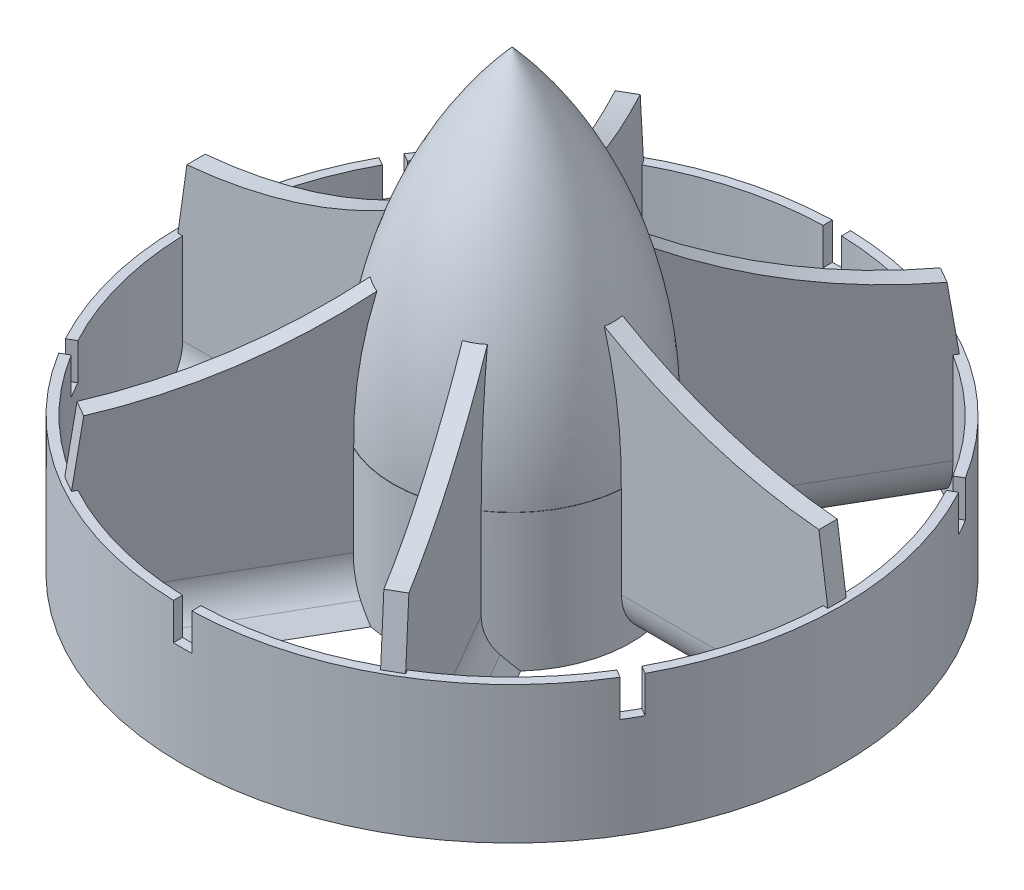
SolidWorks part; units mm, degrees
ref_plane "Ön Düzlem" through (0, 0, 0) normal (0, 0, 1) x (1, 0, 0)
ref_plane "Üst Düzlem" through (0, 0, 0) normal (0, 1, 0) x (1, 0, 0)
ref_plane "Sağ Düzlem" through (0, 0, 0) normal (1, 0, 0) x (0, 0, -1)
sketch "Çizim1" plane through (0, 0, 0) normal (0, 1, 0) x (1, 0, 0)
  circle A0 centre (0, 0) radius 13
  circle A1 centre (0, 0) radius 35
  circle A2 centre (0, 0) radius 36
  dimension "D1" = 26
  dimension "D2" = 70
extrude "Yükseklik-Ekstrüzyon1" add sketch "Çizim1" along normal blind 15 contours A0 region at (0, 0, 0)
extrude "Yükseklik-Ekstrüzyon2" add sketch "Çizim1<3>" along normal blind 15 separate body contours A2 | A1
sketch "Çizim1<3>" plane through (0, 0, 0) normal (0, 1, 0) x (1, 0, 0) same geometry as "Çizim1"
sketch "Çizim4" plane through (0, 0, 0) normal (1, 0, 0) x (0, 0, -1)
  line L1 (-36, 0) -> (36, 0) construction
  line L4 (1, 3) -> (1, 38)
  line L5 (1, 38) -> (-1, 38)
  line L6 (-1, 38) -> (-1, 0)
  line L8 (-1, 0) -> (4, 0)
  line L9 (4, 0) -> (1, 3)
  dimension "D2" = 2
extrude "Yükseklik-Ekstrüzyon5" add sketch "Çizim4" along normal blind 35.5 contours L5 L6 L8 L9 L4
fillet "Radyus5" radius 5 1 edges at (23.9736, 0, 1)
fillet "Radyus6" radius 5 1 edges at (23.9736, 3, -1)
ref_axis "Eksen1" through (0, 70.3345, 0) along (0, -1, 0)
pattern_circular "Dairesel Kaplama1" count 6 over 360 about axis through (0, 70.3345, 0) along (0, -1, 0) of "Yükseklik-Ekstrüzyon5", "Radyus5", "Radyus6"
sketch "Çizim8" plane through (0, 0, 0) normal (0, 0, 1) x (1, 0, 0)
  line L3 (35.5, 38) -> (35.5, 21.8859)
  line L4 (35.5, 38) -> (35.5, 15) construction
  line L5 (35.5, 38) -> (1.7321, 38) construction
  line L6 (0, 38) -> (35.5, 38)
  line L7 (16.884, 38) -> (0, 38) construction
  arc A0 (35.5, 21.8859) -> (0, 38) centre (39.5056, 77.8713) cw
extrude "Kes-Ekstrüzyon1" cut sketch "Çizim8" against normal blind 1 and the other way blind 1
pattern_circular "Dairesel Kaplama2" count 6 over 360 about axis through (0, 70.3345, 0) along (0, -1, 0) of "Kes-Ekstrüzyon1"
sketch "Çizim12" plane through (0, 0, 0) normal (0, 0, 1) x (1, 0, 0)
  line L0 (0, 15) -> (12.97, 15)
  line L1 (36, 15) -> (-36, 15) construction
  line L2 (0, 15) -> (0, 49.8724)
  line L3 (0, 70.3345) -> (0, -0.3415) construction
  arc A0 (0, 49.8724) -> (12.97, 15) centre (-38.174, 15.8263) cw
revolve "Döndür1" add sketch "Çizim12" angle 360 about axis through (0, 70.3345, 0) along (0, -1, 0)
sketch "Çizim13" plane through (0, 0, 0) normal (0, 0, 1) x (1, 0, 0)
  line L0 (-1, 15) -> (1, 15)
  line L2 (5.5997, 15) -> (-5.5997, 15) construction
  line L3 (1, 15) -> (1, 11)
  line L4 (1, 11) -> (-1, 11)
  line L5 (-1, 11) -> (-1, 15)
extrude "Kes-Ekstrüzyon2" cut sketch "Çizim13" against normal blind 10 from offset 40
pattern_circular "Dairesel Kaplama7" count 6 over 360 about axis through (0, 70.3345, 0) along (0, -1, 0) of "Kes-Ekstrüzyon2"
sketch "Çizim15" plane through (0, 0, 0) normal (0, 0, 1) x (1, 0, 0)
  line L0 (35.5, 15) -> (34.3866, 22.9221)
  line L1 (34.3866, 22.9221) -> (38.0133, 23.4318)
  line L2 (38.0133, 23.4318) -> (35.5, 15)
extrude "Kes-Ekstrüzyon3" cut sketch "Çizim15" against normal blind 1 and the other way blind 1
pattern_circular "Dairesel Kaplama8" count 6 over 360 about axis through (0, 70.3345, 0) along (0, -1, 0) of "Kes-Ekstrüzyon3"
